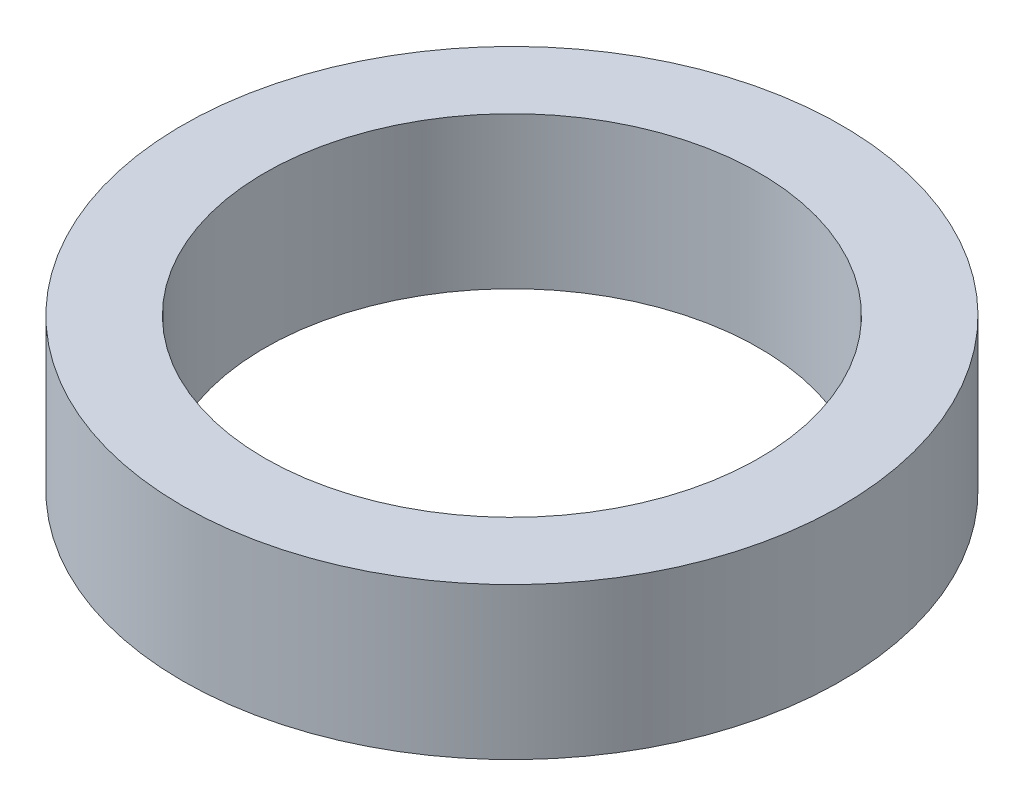
SolidWorks part; units mm, degrees
ref_plane "Front Plane" through (0, 0, 0) normal (0, 0, 1) x (1, 0, 0)
ref_plane "Top Plane" through (0, 0, 0) normal (0, 1, 0) x (1, 0, 0)
ref_plane "Right Plane" through (0, 0, 0) normal (1, 0, 0) x (0, 0, -1)
sketch "Sketch1" plane through (0, 0, 0) normal (0, 1, 0) x (1, 0, 0)
  circle A0 centre (0, 0) radius 50
  dimension "FLANGE_OD" = 100
extrude "Boss-Extrude1" add sketch "Sketch1" along normal blind 23
sketch "Sketch2" plane through (0, 0, 0) normal (0, 1, 0) x (1, 0, 0)
  circle A0 centre (0, 0) radius 37.5
  dimension "BORE_D" = 75
extrude "Cut-Extrude1" cut sketch "Sketch2" along normal through all
sketch "Sketch3" plane through (0, 23, 0) normal (0, 1, 0) x (1, 0, 0)
  circle A0 centre (0, 0) radius 20.292 construction
  circle A1 centre (-20.292, 0) radius 1.5948
  dimension "BOLT_D" = 3.1897
  dimension "BOLT_PCD" = 40.584
extrude "Cut-Extrude2" cut sketch "Sketch3" against normal blind 22.9201 rebuild error yes
pattern_circular "CirPattern1" count 4 over 360 rebuild error yes
